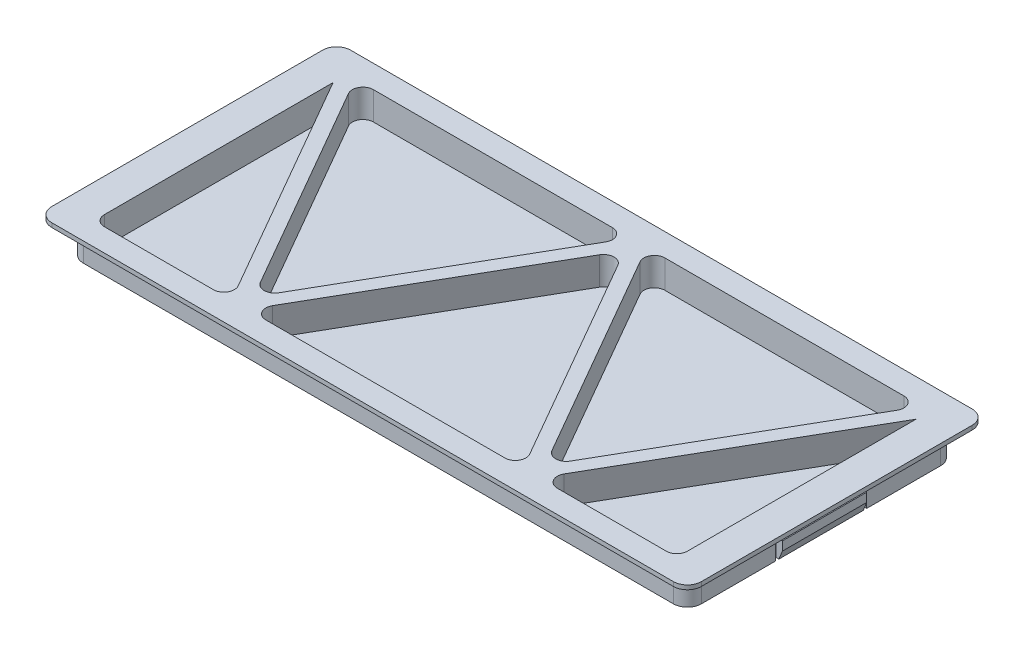
SolidWorks part; units mm, degrees
ref_plane "Front Plane" through (0, 0, 0) normal (0, 0, 1) x (1, 0, 0)
ref_plane "Top Plane" through (0, 0, 0) normal (0, 1, 0) x (1, 0, 0)
ref_plane "Right Plane" through (0, 0, 0) normal (1, 0, 0) x (0, 0, -1)
sketch "Sketch1" plane through (0, 0, 0) normal (0, 1, 0) x (1, 0, 0)
  line L1 (44.05, -19.05) -> (-44.05, -19.05)
  line L2 (44.05, -19.05) -> (44.05, 19.05)
  line L3 (44.05, 19.05) -> (-44.05, 19.05)
  line L4 (-44.05, -19.05) -> (-44.05, 19.05)
  line L5 (44.05, -19.05) -> (-44.05, 19.05) construction
  line L6 (44.05, 19.05) -> (-44.05, -19.05) construction
  point P0 (0, 0)
  dimension "D1" = 88.1
  dimension "D2" = 38.1
extrude "Boss-Extrude1" add sketch "Sketch1" along normal blind 5
shell "Shell1" thickness 1 removed face at (0, 5, 0)
sketch "Sketch2" plane through (0, 5, 0) normal (0, 1, 0) x (1, 0, 0)
  line L0 (-46.3, 21.3) -> (-46.3, -21.3)
  line L1 (-46.3, -21.3) -> (46.3, -21.3)
  line L2 (46.3, -21.3) -> (46.3, 21.3)
  line L3 (46.3, 21.3) -> (-46.3, 21.3)
  line L4 (-44.05, 19.05) -> (-44.05, -19.05)
  line L5 (-44.05, -19.05) -> (44.05, -19.05)
  line L6 (44.05, -19.05) -> (44.05, 19.05)
  line L7 (44.05, 19.05) -> (-44.05, 19.05)
  line L8 (-44.05, 19.05) -> (-44.05, -19.05)
  line L9 (-44.05, -19.05) -> (44.05, -19.05)
  line L10 (44.05, -19.05) -> (44.05, 19.05)
  line L11 (44.05, 19.05) -> (-44.05, 19.05)
  dimension "D1" = 0
  dimension "D2" = 2.25
extrude "Boss-Extrude2" add sketch "Sketch2" against normal blind 0.6
sketch "Sketch5" plane through (0, 0, 0) normal (0, -1, 0) x (1, 0, 0)
  line L0 (44.05, 19.05) -> (44.05, -19.05) construction
  line L1 (44.05, 19.05) -> (41.55, 19.05)
  line L2 (44.05, 19.05) -> (44.05, -19.05)
  line L3 (44.05, -19.05) -> (41.55, -19.05)
  line L4 (41.55, 19.05) -> (41.55, -19.05)
  line L5 (44.05, 6.5) -> (42.55, 6.5) construction
  line L6 (42.55, 6.5) -> (42.55, -6.5) construction
  line L7 (42.55, -6.5) -> (44.05, -6.5) construction
  point P6 (41.55, 0)
  point P12 (42.55, 0)
  dimension "D1" = 1
  dimension "D3" = 1.5
  dimension "D4" = 13
extrude "Boss-Extrude4" add sketch "Sketch5" against normal up to surface (5 mm away) up to face at (0, 5, 0)
sketch "Sketch7" plane through (0, 0, 0) normal (0, -1, 0) x (1, 0, 0)
  line L0 (41.55, 19.05) -> (41.55, -19.05) construction
  line L1 (42.05, 6.515) -> (44.05, 6.515)
  line L2 (42.05, 6.515) -> (42.05, -6.5)
  line L3 (42.05, -6.5) -> (44.05, -6.5)
  line L4 (44.05, 6.515) -> (44.05, -6.5)
  dimension "D1" = 0.5
extrude "Cut-Extrude2" cut sketch "Sketch7" against normal up to surface (4.4 mm away) up to face at (0, 4.4, 0)
sketch "Sketch8" plane through (0, 4.4, 0) normal (0, -1, 0) x (1, 0, 0)
  line L0 (44.05, -6.5) -> (44.05, -19.05) construction
  line L1 (44.05, 6.015) -> (43.65, 6.015)
  line L2 (44.05, 6.015) -> (44.05, -6.015)
  line L3 (44.05, -6.015) -> (43.65, -6.015)
  line L4 (43.65, 6.015) -> (43.65, -6.015)
  line L5 (44.05, 6.515) -> (42.05, 6.515) construction
  point P10 (43.65, 0)
  dimension "D1" = 0.4
  dimension "D2" = 0.5
extrude "Boss-Extrude5" add sketch "Sketch8" along normal up to surface (4.4 mm away) up to face at (21.525, 0, 0.0037)
sketch "Sketch9" plane through (0, 0, -6.015) normal (0, 0, -1) x (-1, 0, 0)
  line L0 (-46.3, 4.4) -> (46.3, 4.4) construction
  line L1 (-44.05, 0) -> (-44.55, 1.2375)
  line L2 (-44.05, 0) -> (-44.05, 2.5)
  line L3 (-44.05, 2.5) -> (-44.55, 2.5)
  line L4 (-44.55, 1.2375) -> (-44.55, 2.5)
  dimension "D1" = 0.5
  dimension "D2" = 1.9
  dimension "D3" = 22
extrude "Boss-Extrude6" add sketch "Sketch9" against normal up to surface (12.03 mm away) up to face at (43.85, 2.2, 6.015)
mirror "Mirror1" about plane through (0, 0, 0) normal (1, 0, 0) of "Boss-Extrude4", "Cut-Extrude2", "Boss-Extrude5", "Boss-Extrude6"
sketch "Sketch3" plane through (0, 5, 0) normal (0, 1, 0) x (1, 0, 0)
  line L0 (-41.55, 18.05) -> (-20.775, -18.05) construction
  line L1 (-41.55, -18.05) -> (41.55, -18.05) construction
  line L2 (-20.775, -18.05) -> (0, 18.05) construction
  line L3 (41.55, 18.05) -> (-41.55, 18.05) construction
  line L4 (0, 18.05) -> (20.775, -18.05) construction
  line L5 (20.775, -18.05) -> (41.55, 18.05) construction
  line L6 (-42.4167, 17.5512) -> (-20.775, -20.0549)
  line L7 (-20.775, -20.0549) -> (0, 16.0451)
  line L8 (0, 16.0451) -> (20.775, -20.0549)
  line L9 (20.775, -20.0549) -> (42.4167, 17.5512)
  line L10 (-40.6833, 18.5488) -> (-20.775, -16.0451)
  line L11 (-20.775, -16.0451) -> (0, 20.0549)
  line L12 (0, 20.0549) -> (20.775, -16.0451)
  line L13 (20.775, -16.0451) -> (40.6833, 18.5488)
  line L14 (-42.4167, 17.5512) -> (-40.6833, 18.5488)
  line L15 (42.4167, 17.5512) -> (40.6833, 18.5488)
  line L16 (-41.55, 18.05) -> (-20.775, -18.05) construction
  line L17 (20.775, -18.05) -> (41.55, 18.05) construction
  line L18 (41.55, 18.05) -> (-41.55, 18.05) construction
  line L19 (41.55, -18.05) -> (41.55, 18.05) construction
  line L20 (-41.55, 18.05) -> (-41.55, -18.05) construction
  line L21 (-41.55, -18.05) -> (-41.55, 18.05) construction
  dimension "D1" = 1
  dimension "D2" = 1
extrude "Boss-Extrude3" add sketch "Sketch3" against normal up to surface (4 mm away) up to face at (0, 1, 0)
sketch "Sketch4" plane through (0, 0, 0) normal (0, -1, 0) x (1, 0, 0)
  line L9 (-44.05, 19.05) -> (44.05, 19.05)
  line L10 (-44.05, 19.05) -> (-44.05, 119.05)
  line L11 (-44.05, 119.05) -> (44.05, 119.05)
  line L12 (44.05, 19.05) -> (44.05, 119.05)
  line L13 (44.05, -19.05) -> (-44.05, -19.05)
  line L14 (44.05, -19.05) -> (44.05, -119.05)
  line L15 (44.05, -119.05) -> (-44.05, -119.05)
  line L16 (-44.05, -19.05) -> (-44.05, -119.05)
  dimension "D1" = 100
  dimension "D2" = 100
extrude "Cut-Extrude1" cut sketch "Sketch4" against normal up to surface (4.4 mm away) up to face at (-43.85, 4.4, 0)
fillet "Fillet1" radius 2 8 edges at (-46.3, 4.7, 21.3) (-44.05, 2.2, 19.05) (-44.05, 2.2, -19.05) (44.05, 2.2, 19.05) (46.3, 4.7, 21.3) (44.05, 2.2, -19.05) (46.3, 4.7, -21.3) (-46.3, 4.7, -21.3)
fillet "Fillet2" radius 1.5 13 edges at (40.3962, 3, -18.05) (20.775, 3, 16.0451) (21.9288, 3, 18.05) (19.6212, 3, 18.05) (0, 3, -16.0451) (1.1538, 3, -18.05) (-1.1538, 3, -18.05) (-19.6212, 3, 18.05) (-21.9288, 3, 18.05) (-20.775, 3, 16.0451) (-40.3962, 3, -18.05) (41.55, 3, 18.05) (-41.55, 3, 18.05)
